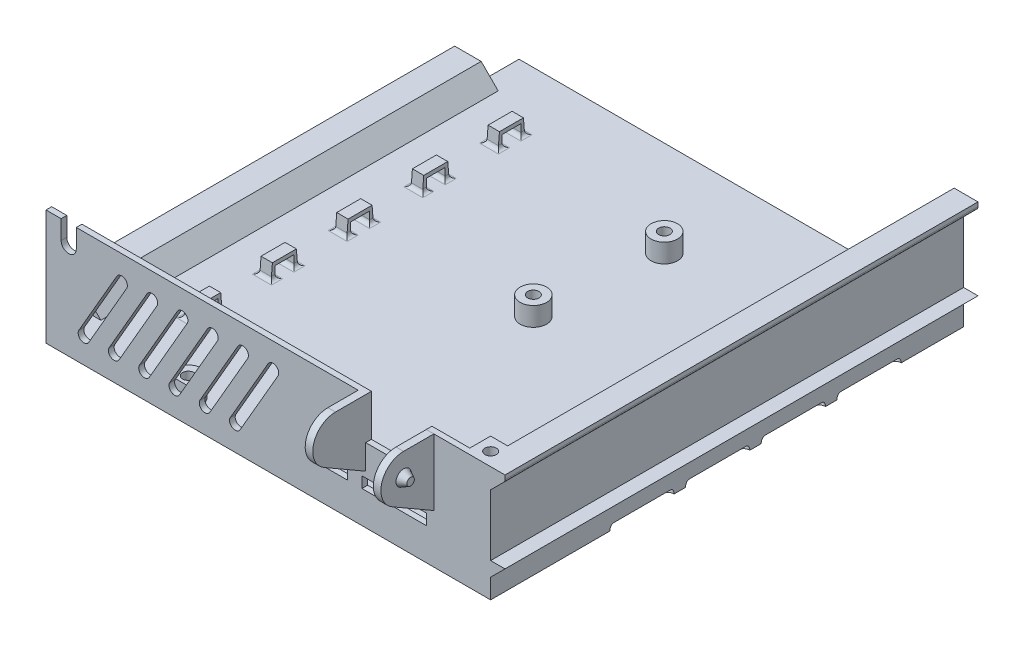
SolidWorks part; units mm, degrees
material "ABS"
ref_plane "Front Plane" through (0, 0, 0) normal (0, 0, 1) x (1, 0, 0)
ref_plane "Top Plane" through (0, 0, 0) normal (0, 1, 0) x (1, 0, 0)
ref_plane "Right Plane" through (0, 0, 0) normal (1, 0, 0) x (0, 0, -1)
ref_axis "Axis1" through (0, 0, 22) along (0, 0, -1)
sketch "Sketch1" plane through (0, 0, 0) normal (0, 1, 0) x (1, 0, 0)
  line L0 (-124.5, 0) -> (0, 0) construction
  line L1 (124.5, 0) -> (124.5, 125) construction
  line L2 (124.5, 125) -> (-124.5, 125) construction
  line L3 (-124.5, 125) -> (-124.5, 0) construction
  line L4 (40.75, 3.85) -> (40.75, 1.6) construction
  line L5 (38.5, 101.6) -> (108.5, 101.6)
  line L6 (38.5, 101.6) -> (38.5, 1.6)
  line L7 (38.5, 1.6) -> (108.5, 1.6)
  line L8 (108.5, 101.6) -> (108.5, 1.6)
  line L9 (38.5, 101.6) -> (108.5, 1.6) construction
  line L10 (38.5, 1.6) -> (108.5, 101.6) construction
  line L11 (40.75, 3.85) -> (38.5, 3.85) construction
  line L12 (-113.79, 77.51) -> (-116.04, 77.51) construction
  line L13 (77.7, 11.6) -> (86.7, 11.6)
  line L14 (77.7, 11.6) -> (77.7, 1.6)
  line L15 (77.7, 1.6) -> (86.7, 1.6)
  line L16 (86.7, 11.6) -> (86.7, 1.6)
  line L17 (77.7, 11.6) -> (86.7, 1.6) construction
  line L18 (77.7, 1.6) -> (86.7, 11.6) construction
  line L19 (90.5, 16.6) -> (107.5, 16.6)
  line L20 (90.5, 16.6) -> (90.5, 1.6)
  line L21 (90.5, 1.6) -> (107.5, 1.6)
  line L22 (107.5, 16.6) -> (107.5, 1.6)
  line L23 (90.5, 16.6) -> (107.5, 1.6) construction
  line L24 (90.5, 1.6) -> (107.5, 16.6) construction
  line L25 (-116.04, 113.59) -> (-92.96, 113.59)
  line L26 (-116.04, 113.59) -> (-116.04, 71.41)
  line L27 (-116.04, 71.41) -> (-92.96, 71.41)
  line L28 (-92.96, 113.59) -> (-92.96, 71.41)
  line L29 (-116.04, 113.59) -> (-92.96, 71.41) construction
  line L30 (-116.04, 71.41) -> (-92.96, 113.59) construction
  line L31 (-113.79, 77.51) -> (-113.79, 71.41) construction
  line L32 (-95.21, 107.49) -> (-95.21, 113.59) construction
  line L33 (-95.21, 107.49) -> (-92.96, 107.49) construction
  line L34 (-64.5, 85.45) -> (-68, 85.45) construction
  line L35 (-65, 88.95) -> (-15, 88.95)
  line L36 (-68, 85.95) -> (-68, 6.95)
  line L37 (-65, 3.95) -> (-15, 3.95)
  line L38 (-12, 85.95) -> (-12, 6.95)
  line L39 (-68, 88.95) -> (-12, 3.95) construction
  line L40 (-68, 3.95) -> (-12, 88.95) construction
  line L41 (-64.5, 85.45) -> (-15.5, 85.45) construction
  line L42 (-64.5, 85.45) -> (-64.5, 27.45) construction
  line L43 (-64.5, 27.45) -> (-15.5, 27.45) construction
  line L44 (-15.5, 85.45) -> (-15.5, 27.45) construction
  line L45 (0, 0) -> (0, 125) construction
  line L46 (0, 0) -> (124.5, 0) construction
  line L47 (-64.5, 85.45) -> (-64.5, 88.95) construction
  line L48 (73.5, 0.1) -> (73.5, 125) construction
  line L49 (-65.69, 22.9) -> (-49.81, 22.9)
  line L50 (-65.69, 22.9) -> (-65.69, 1.5)
  line L51 (-65.69, 1.5) -> (-49.81, 1.5)
  line L52 (-49.81, 22.9) -> (-49.81, 1.5)
  line L53 (-65.69, 22.9) -> (-49.81, 1.5) construction
  line L54 (-65.69, 1.5) -> (-49.81, 22.9) construction
  line L55 (-45.65, 19.42) -> (-32.35, 19.42)
  line L56 (-45.65, 19.42) -> (-45.65, 1.5)
  line L57 (-45.65, 1.5) -> (-32.35, 1.5)
  line L58 (-32.35, 19.42) -> (-32.35, 1.5)
  line L59 (-45.65, 19.42) -> (-32.35, 1.5) construction
  line L60 (-45.65, 1.5) -> (-32.35, 19.42) construction
  line L61 (-27.65, 19.42) -> (-14.35, 19.42)
  line L62 (-27.65, 19.42) -> (-27.65, 1.5)
  line L63 (-27.65, 1.5) -> (-14.35, 1.5)
  line L64 (-14.35, 19.42) -> (-14.35, 1.5)
  line L65 (-27.65, 19.42) -> (-14.35, 1.5) construction
  line L66 (-27.65, 1.5) -> (-14.35, 19.42) construction
  line L67 (-40, 0) -> (-40, 125) construction
  line L68 (-113.79, 11.41) -> (-113.79, 17.51) construction
  line L69 (-116.04, 53.59) -> (-92.96, 53.59)
  line L70 (-116.04, 53.59) -> (-116.04, 11.41)
  line L71 (-116.04, 11.41) -> (-92.96, 11.41)
  line L72 (-92.96, 53.59) -> (-92.96, 11.41)
  line L73 (-116.04, 53.59) -> (-92.96, 11.41) construction
  line L74 (-116.04, 11.41) -> (-92.96, 53.59) construction
  line L75 (-113.79, 17.51) -> (-116.04, 17.51) construction
  line L76 (-95.21, 53.59) -> (-95.21, 47.49) construction
  line L77 (-95.21, 47.49) -> (-92.96, 47.49) construction
  line L78 (-104.5, 0) -> (-104.5, 32.5) construction
  line L79 (-104.5, 32.5) -> (-104.5, 92.5) construction
  line L80 (-104.5, 92.5) -> (-104.5, 125) construction
  line L81 (-64.5, 27.45) -> (-15.5, 85.45) construction
  line L82 (-15.5, 27.45) -> (-64.5, 85.45) construction
  circle A0 centre (105.5, 81.6) radius 1.75
  circle A1 centre (105.5, 19.6) radius 1.75
  circle A2 centre (70.6, 99.8) radius 1.75
  circle A3 centre (67.8, 68) radius 1.75
  circle A4 centre (40.75, 3.85) radius 1.75
  circle A5 centre (-95.21, 107.49) radius 1.4
  circle A6 centre (-113.79, 77.51) radius 1.4
  arc A7 (-15, 3.95) -> (-12, 6.95) centre (-15, 6.95) ccw
  arc A8 (-68, 6.95) -> (-65, 3.95) centre (-65, 6.95) ccw
  arc A9 (-15, 88.95) -> (-12, 85.95) centre (-15, 85.95) cw
  arc A10 (-65, 88.95) -> (-68, 85.95) centre (-65, 85.95) ccw
  circle A11 centre (-64.5, 85.45) radius 1.375
  circle A12 centre (-15.5, 85.45) radius 1.375
  circle A13 centre (-64.5, 27.45) radius 1.375
  circle A14 centre (-15.5, 27.45) radius 1.375
  circle A15 centre (-95.21, 47.49) radius 1.4
  circle A16 centre (-113.79, 17.51) radius 1.4
  circle A17 centre (40.75, 3.85) radius 2.84
  point P0 (73.5, 51.6)
  point P3 (-104.5, 92.5)
  point P4 (0, 0)
  point P24 (82.2, 6.6)
  point P30 (99, 9.1)
  point P47 (-40, 46.45)
  point P65 (-39, 10.46)
  point P69 (-57.75, 12.2)
  point P84 (-21, 10.46)
  point P89 (-104.5, 32.5)
  point P111 (-40, 56.45)
  dimension "D5" = 3.5
  dimension "D26" = 3
  dimension "D27" = 2.75
  dimension "D44" = 2.8
  dimension "D49" = 5.68
  dimension "D1" = 249
  dimension "D2" = 125
  dimension "D3" = 100
  dimension "D4" = 70
  dimension "D6" = 20
  dimension "D7" = 3
  dimension "D8" = 82
  dimension "D9" = 1.8
  dimension "D10" = 37.9
  dimension "D11" = 33.6
  dimension "D12" = 40.7
  dimension "D13" = 2.25
  dimension "D14" = 9
  dimension "D15" = 10
  dimension "D16" = 26.3
  dimension "D17" = 17
  dimension "D18" = 15
  dimension "D19" = 9.5
  dimension "D20" = 23.08
  dimension "D21" = 42.18
  dimension "D22" = 6.1
  dimension "D23" = 2.25
  dimension "D24" = 85
  dimension "D25" = 56
  dimension "D28" = 58
  dimension "D29" = 49
  dimension "D30" = 10.25
  dimension "D31" = 29
  dimension "D32" = 47
  dimension "D33" = 21.4
  dimension "D34" = 15.88
  dimension "D35" = 2.45
  dimension "D36" = 13.3
  dimension "D37" = 17.92
  dimension "D38" = 2.45
  dimension "D39" = 2.45
  dimension "D40" = 2.25
  dimension "D41" = 1.6
  dimension "D42" = 40
  dimension "D43" = 1.5
  dimension "D45" = 60
  dimension "D46" = 3.5
  dimension "D47" = 20
  dimension "D48" = 16
sketch "Sketch2" plane through (0, 0, 0) normal (0, 1, 0) x (1, 0, 0)
  line L0 (124.5, 125) -> (-124.5, 125) construction
  line L1 (124.5, 0) -> (7, 0)
  line L2 (124.5, 0) -> (124.5, 125)
  line L3 (124.5, 125) -> (7, 125)
  line L4 (7, 0) -> (7, 125)
  line L5 (124.5, 0) -> (7, 125) construction
  line L6 (124.5, 125) -> (7, 0) construction
  point P4 (65.75, 62.5)
  dimension "D1" = 7
extrude "Boss-Extrude1" add sketch "Sketch2" along normal blind 2.5
sketch "Sketch3" plane through (0, 2.5, 0) normal (0, 1, 0) x (1, 0, 0)
  circle A0 centre (105.5, 19.6) radius 1.5
  circle A1 centre (67.8, 68) radius 1.5
  circle A2 centre (105.5, 81.6) radius 1.5
  circle A3 centre (70.6, 99.8) radius 1.5
  circle A4 centre (40.75, 3.85) radius 1.5
  circle A5 centre (40.75, 3.85) radius 3.5
  circle A6 centre (105.5, 19.6) radius 3.5
  circle A7 centre (67.8, 68) radius 3.5
  circle A8 centre (105.5, 81.6) radius 3.5
  circle A9 centre (70.6, 99.8) radius 3.5
  dimension "D1" = 3
  dimension "D2" = 2
extrude "Boss-Extrude2" add sketch "Sketch3" along normal blind 5
sketch "Sketch5" plane through (0, 2.5, 0) normal (0, 1, 0) x (1, 0, 0)
  line L0 (124.5, 0) -> (124.5, 125) construction
  line L1 (7, 0) -> (124.5, 0)
  line L2 (7, 0) -> (7, 1.5)
  line L3 (7, 1.5) -> (124.5, 1.5)
  line L4 (124.5, 0) -> (124.5, 1.5)
  line L5 (7, 0) -> (124.5, 1.5) construction
  line L6 (7, 1.5) -> (124.5, 0) construction
  point P4 (65.75, 0.75)
  dimension "D1" = 1.5
extrude "Boss-Extrude3" add sketch "Sketch5" along normal blind 28
sketch "Sketch6" plane through (0, 0, 0) normal (0, 0, 1) x (1, 0, 0)
  line L0 (77.7, 0) -> (86.7, 0) construction
  line L1 (77.7, 0) -> (86.7, 0) construction
  line L2 (90.5, 0) -> (107.5, 0) construction
  line L3 (90.5, 0) -> (107.5, 0) construction
  line L4 (77.7, 0) -> (77.7, 2.5) construction
  line L5 (77.7, 2.5) -> (77.7, 7.5) construction
  line L6 (77.7, 7.5) -> (77.7, 8.5) construction
  line L7 (77.7, 8.5) -> (86.7, 8.5)
  line L8 (86.7, 8.5) -> (86.7, 13.6)
  line L9 (86.7, 13.6) -> (77.7, 13.6)
  line L10 (77.7, 13.6) -> (77.7, 8.5)
  line L11 (90.5, 8.5) -> (107.5, 8.5)
  line L12 (107.5, 8.5) -> (107.5, 11.4)
  line L13 (107.5, 11.4) -> (90.5, 11.4)
  line L14 (90.5, 11.4) -> (90.5, 8.5)
  line L15 (77.7, 8.5) -> (86.7, 13.6) construction
  line L16 (77.7, 13.6) -> (86.7, 8.5) construction
  line L18 (76.45, 15.8) -> (87.95, 15.8) construction
  line L19 (76.45, 15.8) -> (76.45, 6.3) construction
  line L20 (76.45, 6.3) -> (87.95, 6.3) construction
  line L21 (87.95, 15.8) -> (87.95, 6.3) construction
  line L22 (76.45, 15.8) -> (87.95, 6.3) construction
  line L23 (76.45, 6.3) -> (87.95, 15.8) construction
  point P9 (82.2, 11.05)
  dimension "D1" = 2.5
  dimension "D2" = 5
  dimension "D3" = 1
  dimension "D4" = 9
  dimension "D5" = 17
  dimension "D6" = 2.9
  dimension "D7" = 5.1
  dimension "D8" = 11.5
  dimension "D9" = 9.5
extrude "Cut-Extrude1" cut sketch "Sketch6" against normal up to surface (1.5 mm away) up to face at (53.25, 10.75, -1.5)
sketch "Sketch7" plane through (0, 0, 0) normal (0, 0, 1) x (1, 0, 0)
  line L0 (124.5, 0) -> (124.5, 5.2)
  line L1 (124.5, 30.5) -> (124.5, 0) construction
  line L2 (124.5, 5.2) -> (126.3, 7)
  line L3 (126.3, 7) -> (126.3, 0) construction
  line L4 (126.3, 0) -> (124.5, 0) construction
  line L5 (126.3, 7) -> (122, 7)
  line L6 (122, 7) -> (122, 0)
  line L7 (7, 0) -> (124.5, 0) construction
  line L8 (122, 0) -> (124.5, 0)
  line L9 (124.5, 7) -> (124.5, 25.2)
  line L10 (126.3, 7) -> (126.3, 27) construction
  line L11 (124.5, 25.2) -> (126.3, 27)
  line L12 (126.3, 0) -> (128.3, 0) construction
  line L13 (128.3, 0) -> (128.3, 29) construction
  line L14 (126.3, 7) -> (128.3, 9)
  line L15 (126.3, 27) -> (128.3, 29)
  line L16 (122, 7) -> (122, 30.5)
  line L17 (7, 30.5) -> (124.5, 30.5) construction
  line L18 (122, 30.5) -> (128.3, 30.5)
  line L19 (128.3, 30.5) -> (128.3, 29)
  line L20 (128.3, 9) -> (122, 9)
  line M19 (7, 0) -> (124.5, 0)
  line M20 (124.5, 0) -> (124.5, 30.5)
  line M21 (124.5, 30.5) -> (7, 30.5)
  dimension "D1" = 5.2
  dimension "D2" = 7
  dimension "D3" = 1.8
  dimension "D4" = 2.5
  dimension "D5" = 25.2
  dimension "D6" = 27
  dimension "D7" = 2
extrude "Boss-Extrude4" add sketch "Sketch7" against normal up to surface (125 mm away) contours L5 L6 M19 M20 | L2 L5 M20 | L14 L20 L5 M20 | L20 L16 L5 M20 | L20 L9 L16 M20 M21 | L19 L18 L11 L15 M20 region at (123.25, 3.5, 0) region at (125.1, 6.4, 0) region at (125.9595, 8.119, 0) region at (123.25, 8, 0) region at (123.25, 19.75, 0) region at (126.0461, 28.623, 0) up to face at (65.75, 1.25, -125)
fillet "Fillet1" radius 1 1 edges at (128.3, 29, -62.5)
sketch "Sketch9" plane through (0, 0, 0) normal (0, 0, 1) x (1, 0, 0)
  line L0 (7, 7) -> (11.5, 2.5)
  line L1 (7, 0) -> (0, 0)
  line L2 (7, 0) -> (7, 7)
  line L3 (7, 7) -> (0, 7)
  line L4 (0, 0) -> (0, 7)
  line L5 (7, 0) -> (0, 7) construction
  line L6 (7, 7) -> (0, 0) construction
  line L7 (11.5, 2.5) -> (7, 2.5)
  line L8 (7, 0) -> (124.5, 0) construction
  circle A0 centre (3.5, 3.5) radius 1.5
  point P4 (3.5, 3.5)
  line M15 (7, 30.5) -> (7, 0)
  dimension "D2" = 3
  dimension "D1" = 7
  dimension "D3" = 2.5
  dimension "D4" = 45
extrude "Boss-Extrude5" add sketch "Sketch9" against normal offset from surface (105 mm away) 10 from offset 10 contours L4 L1 L2 L3 A0 M15 | L7 L0 M15 region at (8.5, 4, 0) region at (6.901, 4.75, 0) up to face at (105.7481, 14.3743, -125) offset against normal yes
sketch "Sketch12" plane through (0, 30.5, 0) normal (0, 1, 0) x (1, 0, 0)
  line L1 (124.5, 0) -> (117.5, 0)
  line L2 (124.5, 0) -> (124.5, 7)
  line L3 (124.5, 7) -> (117.5, 7)
  line L4 (117.5, 0) -> (117.5, 7)
  line L5 (124.5, 0) -> (117.5, 7) construction
  line L6 (124.5, 7) -> (117.5, 0) construction
  circle A0 centre (121, 3.5) radius 1.5 construction
  point P4 (121, 3.5)
  dimension "D2" = 3
  dimension "D1" = 7
extrude "Boss-Extrude7" add sketch "Sketch12" against normal up to surface (28 mm away) up to face at (37.65, 2.5, -51.185)
sketch "Sketch13" plane through (0, 30.5, 0) normal (0, 1, 0) x (1, 0, 0)
  circle A0 centre (121, 3.5) radius 1.5 construction
  circle A1 centre (121, 3.5) radius 1.5
extrude "Cut-Extrude3" cut sketch "Sketch13" against normal blind 10
sketch "Sketch15" plane through (0, 0, 0) normal (-1, 0, 0) x (0, 0, 1)
  line L0 (-125, 2.5) -> (-1.5, 2.5) construction
  line L1 (-107.5, 2.5) -> (-108.5, 2.5)
  line L2 (-107.5, 2.5) -> (-102.5, 2.5) construction
  line L3 (-107.5, 2.5) -> (-107.5, 5.5)
  line L4 (-107.5, 5.5) -> (-102.5, 5.5)
  line L5 (-102.5, 2.5) -> (-102.5, 5.5)
  line L6 (-107.5, 2.5) -> (-102.5, 5.5) construction
  line L7 (-107.5, 5.5) -> (-102.5, 2.5) construction
  line L8 (-108.5, 2.5) -> (-108.1701, 6.5)
  line L9 (-108.1701, 6.5) -> (-101.8299, 6.5)
  line L10 (-101.8299, 6.5) -> (-101.5, 2.5)
  line L11 (-101.5, 2.5) -> (-102.5, 2.5)
  line L12 (-115, 7) -> (-115, 0) construction
  point P8 (-105, 4)
  dimension "D1" = 3
  dimension "D2" = 5
  dimension "D3" = 1
  dimension "D4" = 1
  dimension "D5" = 0.75
  dimension "D6" = 10
extrude "Boss-Extrude8" add sketch "Sketch15" along normal blind 3 from offset 25 offset against normal yes
pattern_linear "LPattern1" count 5 spacing 20 along (0, 0, 1) of "Boss-Extrude8"
fillet "Fillet2" radius 1 40 edges at (25, 2.5, -62) (23.5, 2.5, -62.5) (23.5, 2.5, -61.5) (22, 2.5, -62) (25, 2.5, -68) (22, 2.5, -68) (23.5, 2.5, -67.5) (23.5, 2.5, -68.5) (25, 2.5, -82) (23.5, 2.5, -82.5) (23.5, 2.5, -81.5) (22, 2.5, -82) (25, 2.5, -88) (23.5, 2.5, -88.5) (23.5, 2.5, -87.5) (22, 2.5, -88) (25, 2.5, -102) (23.5, 2.5, -102.5) (23.5, 2.5, -101.5) (22, 2.5, -102) (25, 2.5, -108) (23.5, 2.5, -108.5) (23.5, 2.5, -107.5) (22, 2.5, -108) (25, 2.5, -22) (23.5, 2.5, -22.5) (23.5, 2.5, -21.5) (22, 2.5, -22) (25, 2.5, -28) (23.5, 2.5, -28.5) (23.5, 2.5, -27.5) (22, 2.5, -28) (25, 2.5, -42) (23.5, 2.5, -42.5) (23.5, 2.5, -41.5) (22, 2.5, -42) (25, 2.5, -48) (23.5, 2.5, -48.5) (23.5, 2.5, -47.5) (22, 2.5, -48)
sketch "Sketch16" plane through (0, 0, 0) normal (0, 0, 1) x (1, 0, 0)
  line L0 (27, 23.9103) -> (17, 6.5897) construction
  line L1 (28.299, 23.1603) -> (18.299, 5.8397)
  line L2 (25.701, 24.6603) -> (15.701, 7.3397)
  line L3 (17, 6.5897) -> (27, 6.5897) construction
  line L4 (27, 6.5897) -> (27, 23.9103) construction
  line L5 (7, 15.25) -> (124.5, 15.25) construction
  line L6 (7, 30.5) -> (7, 0) construction
  line L7 (124.5, 25.2) -> (124.5, 9) construction
  arc A0 (28.299, 23.1603) -> (25.701, 24.6603) centre (27, 23.9103) ccw
  arc A1 (15.701, 7.3397) -> (18.299, 5.8397) centre (17, 6.5897) ccw
  point P2 (22, 15.25)
  dimension "D3" = 1.5
  dimension "D1" = 60
  dimension "D2" = 20
  dimension "D4" = 15
extrude "Cut-Extrude4" cut sketch "Sketch16" against normal up to surface (1.5 mm away) up to face at (82.2, 11.05, -1.5)
pattern_linear "LPattern2" count 6 spacing 8 along (1, 0, 0) of "Cut-Extrude4"
ref_plane "Plane2" through (59.75, -59.75, 0) normal (-0.7071, 0.7071, 0) x (0, 0, 1)
sketch "Sketch18" plane through (59.75, -59.75, 0) normal (-0.7071, 0.7071, 0) x (0, 0, 1)
  line L0 (-107.5, 88.0348) -> (-92.5, 88.0348) construction
  line L1 (-125, 88.0348) -> (-7, 88.0348) construction
  line L2 (-107.5, 89.0348) -> (-92.5, 89.0348)
  line L3 (-107.5, 87.0348) -> (-92.5, 87.0348)
  arc A0 (-107.5, 89.0348) -> (-107.5, 87.0348) centre (-107.5, 88.0348) ccw
  arc A1 (-92.5, 87.0348) -> (-92.5, 89.0348) centre (-92.5, 88.0348) ccw
  point P4 (-100, 88.0348)
  dimension "D1" = 15
  dimension "D2" = 1
  dimension "D3" = 25
extrude "Cut-Extrude5" cut sketch "Sketch18" against normal through all both and the other way through all
pattern_linear "LPattern3" count 4 spacing 20 along (0, 0, 1) of "Cut-Extrude5"
ref_plane "Plane3" through (99.5, 0, 0) normal (1, 0, 0) x (0, 0, -1)
ref_plane "Plane4" through (109.5, 0, 0) normal (1, 0, 0) x (0, 0, -1)
sketch "Sketch20" plane through (109.5, 0, 0) normal (1, 0, 0) x (0, 0, -1)
  line L0 (0, 25.2) -> (0, 9) construction
  line L1 (125, 30.5) -> (0, 30.5) construction
  line L2 (-8, 30.5) -> (0, 30.5)
  line L3 (-11, 19.3038) -> (0, 12.953)
  line L4 (0, 30.5) -> (0, 12.953)
  arc A0 (-8, 30.5) -> (-11, 19.3038) centre (-8, 24.5) ccw
  dimension "D1" = 12
  dimension "D3" = 60
  dimension "D2" = 8
extrude "Boss-Extrude9" add sketch "Sketch20" against normal blind 2 separate body
ref_plane "Plane5" through (0, 0, 8) normal (0, 0, 1) x (1, 0, 0)
sketch "Sketch24" plane through (0, 0, 8) normal (0, 0, 1) x (1, 0, 0)
  line L0 (109.5, 24.5) -> (111.34, 24.5)
  line L1 (111.34, 24.5) -> (111.34, 25.5)
  line L2 (111.34, 25.5) -> (109.5, 26.5)
  line L3 (109.5, 26.5) -> (109.5, 24.5)
  dimension "D1" = 1.84
  dimension "D2" = 2
  dimension "D3" = 1
revolve "Revolve1" add sketch "Sketch24" angle 360 about L0
mirror "Mirror2" about plane through (99.5, 0, 0) normal (1, 0, 0) of "Revolve1", "Boss-Extrude9"
sketch "Sketch25" plane through (0, 0, 0) normal (0, 0, 1) x (1, 0, 0)
  line L0 (107.5, 30.5) -> (107.5, 19.3038) construction
  line L1 (91.5, 30.5) -> (107.5, 30.5)
  line L2 (91.5, 30.5) -> (91.5, 19.5)
  line L3 (91.5, 19.5) -> (107.5, 19.5)
  line L4 (107.5, 30.5) -> (107.5, 19.5)
  line L5 (91.5, 30.5) -> (107.5, 19.5) construction
  line L6 (91.5, 19.5) -> (107.5, 30.5) construction
  point P4 (99.5, 25)
  dimension "D1" = 11
extrude "Cut-Extrude6" cut sketch "Sketch25" against normal up to surface (1.5 mm away) up to face at (38, 15.25, -1.5)
sketch "Sketch26" plane through (0, 0, 0) normal (0, 0, 1) x (1, 0, 0)
  line L0 (13, 30.5) -> (13, 25.5) construction
  line L1 (7, 30.5) -> (89.5, 30.5) construction
  line L2 (15, 30.5) -> (15, 25.5)
  line L3 (11, 30.5) -> (11, 25.5)
  line L4 (7, 30.5) -> (7, 0) construction
  line L5 (11, 30.5) -> (15, 30.5)
  arc A0 (15, 30.5) -> (11, 30.5) centre (13, 30.5) ccw
  arc A1 (11, 25.5) -> (15, 25.5) centre (13, 25.5) ccw
  point P4 (13, 28)
  line M41 (89.5, 30.5) -> (7, 30.5)
  dimension "D1" = 5
  dimension "D2" = 2
  dimension "D3" = 6
extrude "Cut-Extrude7" cut sketch "Sketch26" against normal up to surface (1.5 mm away) contours L3 A1 L2 L5 M41 region at (13, 27.1994, 0) up to face at (62.2376, 15.6325, -1.5)
equation "\"D16@Sketch1\"=22.8+3.5"
equation "\"D19@Sketch1\"=6+3.5"
equation "\"D1@Boss-Extrude3\"=33-2.5-2.5"
